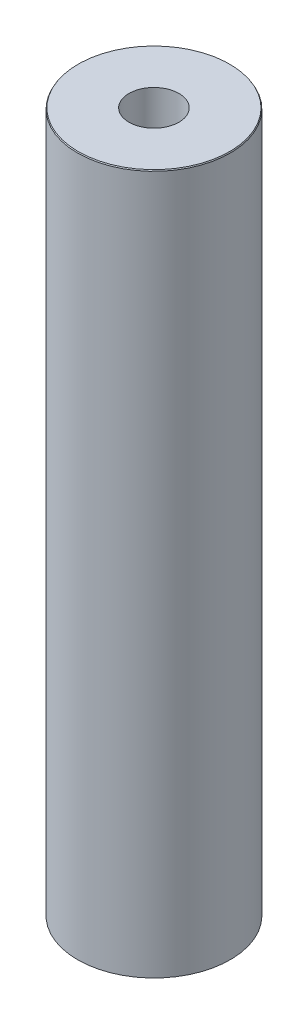
SolidWorks part; units mm, degrees
ref_plane "Front Plane" through (0, 0, 0) normal (0, 0, 1) x (1, 0, 0)
ref_plane "Top Plane" through (0, 0, 0) normal (0, 1, 0) x (1, 0, 0)
ref_plane "Right Plane" through (0, 0, 0) normal (1, 0, 0) x (0, 0, -1)
sketch "Sketch1" plane through (0, 0, 0) normal (0, 1, 0) x (1, 0, 0)
  circle A0 centre (0, 0) radius 20
  dimension "SHAFT_OD" = 40
extrude "Boss-Extrude1" add sketch "Sketch1" along normal blind 183.4777
sketch "Sketch2" plane through (0, 0, 0) normal (0, 1, 0) x (1, 0, 0)
  circle A0 centre (0, 0) radius 6.5436
  dimension "BORE_D" = 13.0871
extrude "Cut-Extrude1" cut sketch "Sketch2" along normal through all
chamfer "Chamfer1" distance 0.269 angle 30 2 edges at (0, 183.4777, 20) (0, 0, 20) first distance on face at (0, 183.4777, 20) first distance on face at (0, 0, 6.5436)
